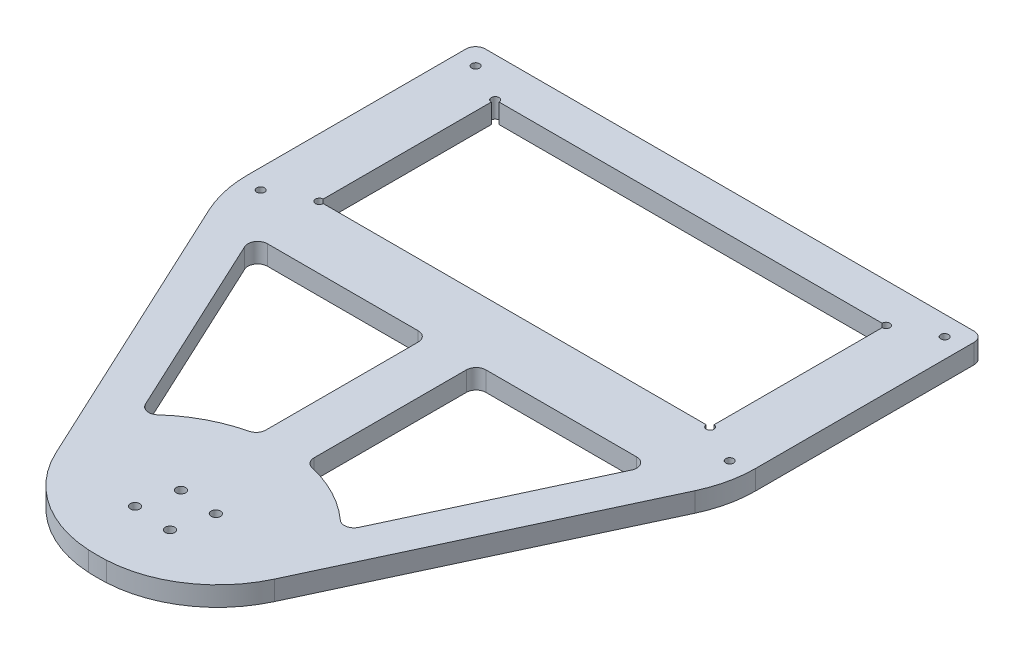
SolidWorks part; units mm, degrees
material "PE High Density"
ref_plane "Front Plane" through (0, 0, 0) normal (0, 0, 1) x (1, 0, 0)
ref_plane "Top Plane" through (0, 0, 0) normal (0, 1, 0) x (1, 0, 0)
ref_plane "Right Plane" through (0, 0, 0) normal (1, 0, 0) x (0, 0, -1)
sketch "Sketch1" plane through (0, 0, 0) normal (0, 1, 0) x (1, 0, 0)
  line L0 (-82.55, -41.275) -> (-28.8775, -156.3761)
  line L1 (-82.55, 41.275) -> (82.55, 41.275)
  line L2 (-82.55, 41.275) -> (-82.55, -41.275)
  line L3 (-82.55, -41.275) -> (82.55, -41.275)
  line L4 (82.55, 41.275) -> (82.55, -41.275)
  line L5 (-82.55, 41.275) -> (82.55, -41.275) construction
  line L6 (-82.55, -41.275) -> (82.55, 41.275) construction
  line L7 (82.55, -41.275) -> (28.8775, -156.3761)
  arc A0 (-28.8775, -156.3761) -> (28.8775, -156.3761) centre (0, -107.0586) ccw
  point P0 (0, 0)
  dimension "D7" = 57.15
  dimension "D1" = 165.1
  dimension "D2" = 82.55
  dimension "D3" = 65
  dimension "D4" = 65
  dimension "D5" = 127
  dimension "D6" = 127
extrude "Boss-Extrude2" add sketch "Sketch1" along normal blind 6.35 contours L0 A0 L7 L3 | L4 L1 L2 L3 region at (0, 0, 91.2149) region at (0, 0, 0)
sketch "Sketch4" plane through (0, 6.35, 0) normal (0, 1, 0) x (1, 0, 0)
  line L0 (0, -164.2086) -> (0, -138.8086) construction
  line L1 (-7.6031, -144.3326) -> (7.6031, -133.2846)
  line L2 (-4.7029, -132.3357) -> (4.7029, -145.2816)
  arc A1 (-28.8775, -156.3761) -> (28.8775, -156.3761) centre (0, -107.0586) ccw construction
  circle A7 centre (-4.7029, -132.3357) radius 1.524
  circle A8 centre (7.6031, -133.2846) radius 1.524
  circle A9 centre (4.7029, -145.2816) radius 1.524
  circle A10 centre (-7.6031, -144.3326) radius 1.524
  point P6 (0, -138.8086)
  point P8 (0, -138.8086)
  dimension "D1" = 18.796
  dimension "D2" = 16.002
  dimension "D4" = 3.048
  dimension "D3" = 25.4
  dimension "D5" = 36
extrude "Cut-Extrude5" cut sketch "Sketch4" against normal through all both and the other way through all contours A9 | A10 | A8 | A7 region at (-6.0224, 6.35, 131.6634) region at (7.1455, 6.35, 131.8762) region at (5.3752, 6.35, 143.9621) region at (-6.1947, 6.35, 143.875)
sketch "Sketch5" plane through (0, 6.35, 0) normal (0, 1, 0) x (1, 0, 0)
  line L0 (-82.55, 41.275) -> (-82.55, -41.275) construction
  line L1 (-82.55, 41.275) -> (82.55, 41.275) construction
  circle A0 centre (-76.2, 34.925) radius 1.27
  circle A1 centre (-76.2, -34.925) radius 1.27
  dimension "D1" = 2.54
  dimension "D4" = 2.54
  dimension "D6" = 76.2
  dimension "D2" = 6.35
  dimension "D3" = 6.35
  dimension "D5" = 6.35
extrude "Cut-Extrude7" cut sketch "Sketch5" against normal through all
mirror "Mirror2" about plane through (0, 0, 0) normal (1, 0, 0) of "Cut-Extrude7"
fillet "Fillet4" radius 38.1 4 edges at (82.55, 3.175, 41.275) (28.8775, 3.175, 156.3761) (-28.8775, 3.175, 156.3761) (-82.55, 3.175, 41.275)
sketch "Sketch7" plane through (0, 6.35, 0) normal (0, 1, 0) x (1, 0, 0)
  line L0 (-82.55, 41.275) -> (82.55, 41.275) construction
  line L1 (-63.5, 28.575) -> (63.5, 28.575)
  line L2 (-63.5, 28.575) -> (-63.5, -28.575)
  line L3 (-63.5, -28.575) -> (63.5, -28.575)
  line L4 (63.5, 28.575) -> (63.5, -28.575)
  line L5 (-63.5, 28.575) -> (63.5, -28.575) construction
  line L6 (-63.5, -28.575) -> (63.5, 28.575) construction
  line L7 (82.55, 41.275) -> (82.55, -32.8284) construction
  circle A0 centre (-63.5, 28.575) radius 1.27
  circle A1 centre (-63.5, -28.575) radius 1.27
  circle A2 centre (63.5, -28.575) radius 1.27
  circle A3 centre (63.5, 28.575) radius 1.27
  point P0 (0, 0)
  dimension "D3" = 2.54
  dimension "D1" = 12.7
  dimension "D2" = 19.05
extrude "Cut-Extrude9" cut sketch "Sketch7" against normal through all both and the other way through all contours A3 L1 A0 L2 A1 L3 A2 L4 | L1 A0 L2 | L2 A0 L1 | L2 A1 L3 | L3 A1 L2 | L3 A2 L4 | L4 A2 L3 | L4 A3 L1 | L4 L3 L2 L1 region at (-63.6797, 6.35, -28.7547) region at (-62.961, 6.35, -28.036) region at (0, 6.35, 0) region at (63.6797, 6.35, -28.7547) region at (-62.961, 6.35, 28.036) region at (-63.6797, 6.35, 28.7547) region at (63.6797, 6.35, 28.7547) region at (62.961, 6.35, 28.036)
sketch "Sketch8" plane through (0, 6.35, 0) normal (0, 1, 0) x (1, 0, 0)
  line L0 (-64.9674, -48.9302) -> (-32.7639, -117.9908)
  line L7 (64.9674, -48.9302) -> (32.7639, -117.9908)
  line L8 (78.9803, -48.9302) -> (35.4944, -142.186) construction
  line L9 (-78.9803, -48.9302) -> (-35.4944, -142.186) construction
  line L10 (-64.9674, -48.9302) -> (64.9674, -48.9302)
  line L12 (-7.8174, -48.9302) -> (-7.8174, -104.1841)
  line L13 (7.8174, -48.9302) -> (7.8174, -104.1841)
  arc A1 (-32.7639, -117.9908) -> (32.7639, -117.9908) centre (0, -147.7492) cw
  dimension "D3" = 44.261
  dimension "D1" = 76.2
  dimension "D2" = 76.2
  dimension "D4" = 12.7
  dimension "D5" = 12.7
  dimension "D6" = 57.15
  dimension "D7" = 57.15
extrude "Cut-Extrude10" cut sketch "Sketch8" against normal through all both and the other way through all contours L0 A1 L12 L10 | L13 A1 L7 L10 region at (-30.4156, 6.35, 76.1401) region at (30.4156, 6.35, 76.1401)
fillet "Fillet5" radius 3.175 10 edges at (64.9674, 3.175, 48.9302) (32.7639, 3.175, 117.9908) (7.8174, 3.175, 104.1841) (7.8174, 3.175, 48.9302) (-7.8174, 3.175, 48.9302) (-7.8174, 3.175, 104.1841) (-32.7639, 3.175, 117.9908) (-64.9674, 3.175, 48.9302) (-82.55, 3.175, -41.275) (82.55, 3.175, -41.275)
